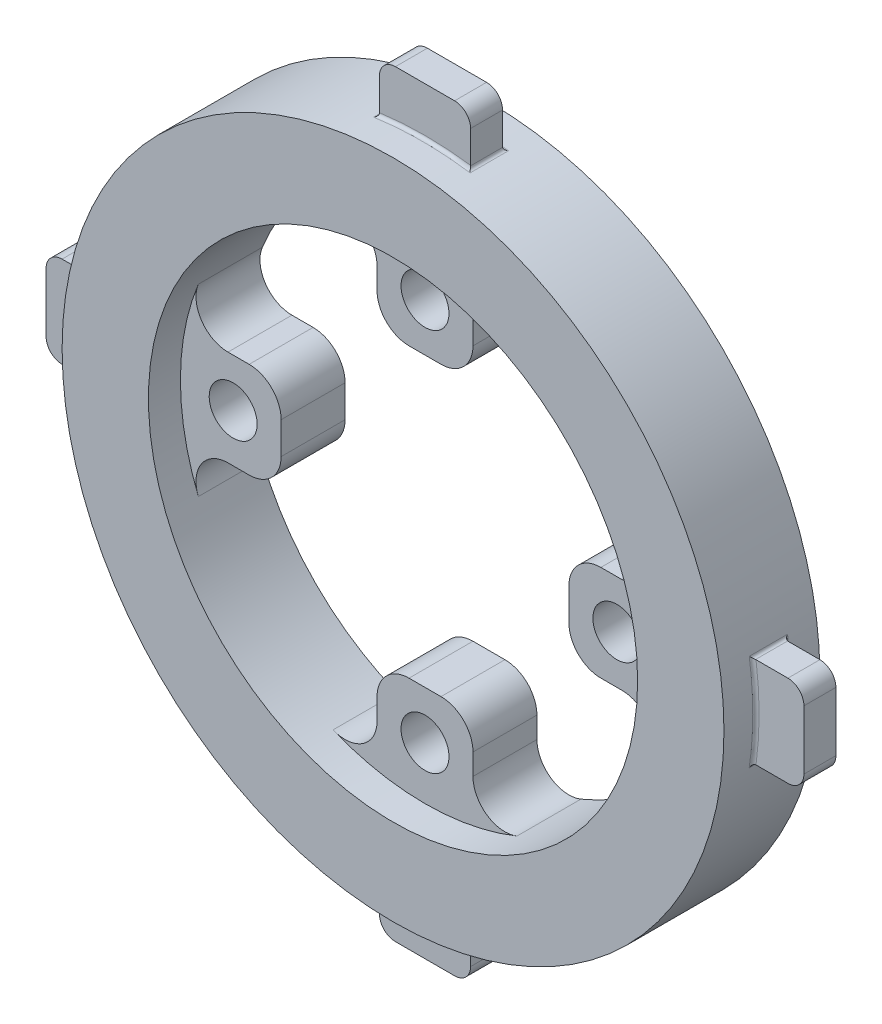
SolidWorks part; units mm, degrees
note: The reader was unsure of these and kept them because the rebuilt part matched: shared geometry of "Sketch2<3>".
material "ABS"
ref_plane "Front Plane" through (0, 0, 0) normal (0, 0, 1) x (1, 0, 0)
ref_plane "Top Plane" through (0, 0, 0) normal (0, 1, 0) x (1, 0, 0)
ref_plane "Right Plane" through (0, 0, 0) normal (1, 0, 0) x (0, 0, -1)
sketch "Sketch1" plane through (0, 0, 0) normal (0, 0, 1) x (1, 0, 0)
  line L0 (0, 0) -> (0, 100) construction
  circle A0 centre (0, 100) radius 7.65
  circle A1 centre (0, 100) radius 10.35
  dimension "D2" = 15.3
  dimension "D1" = 100
  dimension "D3" = 2.7
extrude "Boss-Extrude1" add sketch "Sketch1" against normal blind 3 contours A1 | A0
sketch "Sketch2" plane through (0, 0, -3) normal (0, 0, -1) x (-1, 0, 0)
  line L0 (0, 89.65) -> (0, 110.35) construction
  line L1 (-10.35, 100) -> (10.35, 100) construction
  line L2 (1.5, 92.4985) -> (1.5, 107.5015)
  line L3 (-7.5015, 98.5) -> (7.5015, 98.5)
  line L4 (-1.5, 92.4985) -> (-1.5, 107.5015)
  line L5 (-7.5015, 101.5) -> (7.5015, 101.5)
  line L6 (0, 100) -> (0, 106)
  line L7 (-1.5, 89.65) -> (-1.5, 110.35) construction
  line L8 (1.5, 89.65) -> (1.5, 110.35) construction
  line L9 (-10.35, 101.5) -> (10.35, 101.5) construction
  line L10 (-10.35, 98.5) -> (10.35, 98.5) construction
  line L11 (0, 100) -> (0, 106) construction
  circle A0 centre (0, 100) radius 10.35 construction
  arc A1 (1.5, 107.5015) -> (-1.5, 107.5015) centre (0, 100) ccw
  arc A2 (7.5015, 98.5) -> (7.5015, 101.5) centre (0, 100) ccw
  arc A3 (-1.5, 92.4985) -> (1.5, 92.4985) centre (0, 100) ccw
  arc A4 (-7.5015, 101.5) -> (-7.5015, 98.5) centre (0, 100) ccw
  circle A5 centre (0, 106) radius 0.75
  circle A9 centre (0, 100) radius 7.65 construction
  circle A15 centre (6, 100) radius 0.75 [skipped]
  circle A16 centre (0, 94) radius 0.75 [skipped]
  circle A17 centre (-6, 100) radius 0.75 [skipped]
  point P7 (0, 100)
  point P10 (0, 100)
  point P33 (0, 100)
  point P36 (0, 100)
  point P38 (0.75, 100.75)
  point P40 (0, 100)
  dimension "D4" = 1.5
  dimension "D3" = 6
  dimension "D6" = 6
  dimension "D1" = 1.5
  dimension "D5" = 4
extrude "Boss-Extrude2" add sketch "Sketch2" against normal blind 2
extrude "Cut-Extrude2" cut sketch "Sketch2<3>" against normal through all
sketch "Sketch2<3>" plane through (0, 0, -3) normal (0, 0, -1) x (-1, 0, 0) same geometry as "Sketch2"
pattern_circular "CirPattern4" count 4 over 360 about axis through (0, 100, 0) along (0, 0, 1) of "Cut-Extrude2"
ref_plane "Plane1" through (-10.35, 0, 0) normal (-1, 0, 0) x (0, 0, 1)
sketch "Sketch5" plane through (-10.35, 0, 0) normal (-1, 0, 0) x (0, 0, 1)
  line L0 (-3, 100) -> (0, 100) construction
  line L1 (0, 89.65) -> (0, 110.35) construction
  line L2 (-2, 101.425) -> (-1, 101.425)
  line L3 (-2, 101.425) -> (-2, 98.575)
  line L4 (-2, 98.575) -> (-1, 98.575)
  line L5 (-1, 101.425) -> (-1, 98.575)
  line L6 (-1, 101.425) -> (-2, 98.575) construction
  point P3 (-2, 100)
  point P12 (-1.5, 100)
  dimension "D2" = 1
  dimension "D1" = 2.85
extrude "Boss-Extrude3" add sketch "Sketch5" along normal blind 1.5 and the other way blind 1.5
fillet "Fillet2" radius 0.5 2 edges at (-11.85, 101.425, -1.5) (-11.85, 98.575, -1.5)
fillet "Fillet3" radius 0.1 4 edges at (-10.35, 100, -1) (-10.2514, 101.425, -1.5) (-10.2514, 98.575, -1.5) (-10.35, 100, -2)
pattern_circular "CirPattern3" count 4 over 360 about axis through (0, 100, 0) along (0, 0, 1) of "Fillet3", "Boss-Extrude3", "Fillet2"
fillet "Fillet4" radius 1 8 edges at (1.5, 107.5015, -2) (1.5, 92.4985, -2) (-1.5, 92.4985, -2) (-1.5, 107.5015, -2) (-7.5015, 98.5, -2) (7.5015, 98.5, -2) (-7.5015, 101.5, -2) (7.5015, 101.5, -2)
sketch "Sketch6" plane through (0, 0, -1) normal (0, 0, 1) x (1, 0, 0)
  line L1 (-4.5, 95.5) -> (4.5, 95.5)
  line L2 (-4.5, 95.5) -> (-4.5, 104.5)
  line L3 (-4.5, 104.5) -> (4.5, 104.5)
  line L4 (4.5, 95.5) -> (4.5, 104.5)
  line L5 (-4.5, 95.5) -> (4.5, 104.5) construction
  line L6 (-4.5, 104.5) -> (4.5, 95.5) construction
  point P0 (0, 100)
  dimension "D1" = 9
  dimension "D2" = 9
extrude "Cut-Extrude1" cut sketch "Sketch6" against normal through all
fillet "Fillet5" radius 1 8 edges at (-1.5, 95.5, -2) (1.5, 95.5, -2) (4.5, 98.5, -2) (4.5, 101.5, -2) (-1.5, 104.5, -2) (1.5, 104.5, -2) (-4.5, 98.5, -2) (-4.5, 101.5, -2)
equation "\"OuterThickness\"= 3mm"
equation "\"MasterFillet\"= 3mm"
equation "\"PartSeperation\"= 6mm"
equation "\"Tolerance\"= 0.15mm"
equation "\"HeightPart\"= 100mm"
equation "\"Holes\"= 1.5mm"
equation "\"D1@Sketch1\"=\"HeightPart\""
equation "\"D2@Sketch1\" = \"SpineDiameter\" + \"Tolerance\" * 2"
equation "\"D3@Sketch2\" = ( \"SpineDiameter\" - \"OuterThickness\" ) / 2"
equation "\"D4@Sketch2\"=\"Holes\""
equation "\"SpineHolderThickness\"= 3mm"
equation "\"D3@Sketch1\"=\"SpineHolderThickness\"-\"Tolerance\"*2"
equation "\"SpineHolderDepth\" = 3mm"
equation "\"D1@Boss-Extrude1\"=\"SpineHolderDepth\""
equation "\"D1@Boss-Extrude2\"= \"SpineHolderDepth\" - \"DiscThickness\""
equation "\"D1@Boss-Extrude3\"=\"SpineHolderThickness\"/2"
equation "\"D2@Boss-Extrude3\"=\"SpineHolderThickness\"/2"
equation "\"MotorLength\" = 40.5mm"
equation "\"MotorWidth\" = 20.3mm"
equation "\"AttachmentHeight\"= 3mm"
equation "\"SpoolDiameter\"= 60mm"
equation "\"SpoolHeight\"= 2mm"
equation "\"SpoolRidgeHeight\"= 1mm"
equation "\"SpoolRidgeDepth\"= 2mm"
equation "\"SpoolSeperation\"= 2mm"
equation "\"ServoHolderWidthOffset\"= 20mm"
equation "\"MotorTransmitterToScrew\"= 21.7mm"
equation "\"SpoolToSpine\"= 15mm"
equation "\"SpoolCenterToMotor\" = 31.5mm"
equation "\"HubOffset\"= 18mm"
equation "\"D2@Sketch5\"=\"SpineHolderDepth\"/3"
equation "\"D1@Sketch5\"=\"SpineHolderThickness\"-\"Tolerance\""
equation "\"D2@Sketch6\" = \"SpineDiameter\" - \"Holes\" * 4"
equation "\"D1@Sketch6\" = \"SpineDiameter\" - \"Holes\" * 4"
equation "\"DiscThickness\"= 4mm"
equation "\"LigamentThickness\"= 2mm"
equation "\"LigamentExtension\"= 1mm"
equation "\"LigamentAngle\"= 20deg"
equation "\"SpineDiameter\"= 15mm"
equation "\"LigamentDepth\"= 1mm"
equation "\"ServoFastenerHolders\"=2mm"
equation "\"ArduinoLength\" = 53.4mm"
equation "\"ArduinoWidth\" = 50mm"
equation "\"ArdYOffset\" = 29.5mm"
equation "\"ArdXOffset\" = 20.5mm"
equation "\"ArdXOffsetSmall\" = 25mm"
equation "\"MiddleServoOffset\"= 12mm"
equation "\"LargeServoOffset\"= 3mm"
equation "\"SmallServoOffset\"= 0mm"
equation "\"ToolHoleDiameter\"= 12mm"
